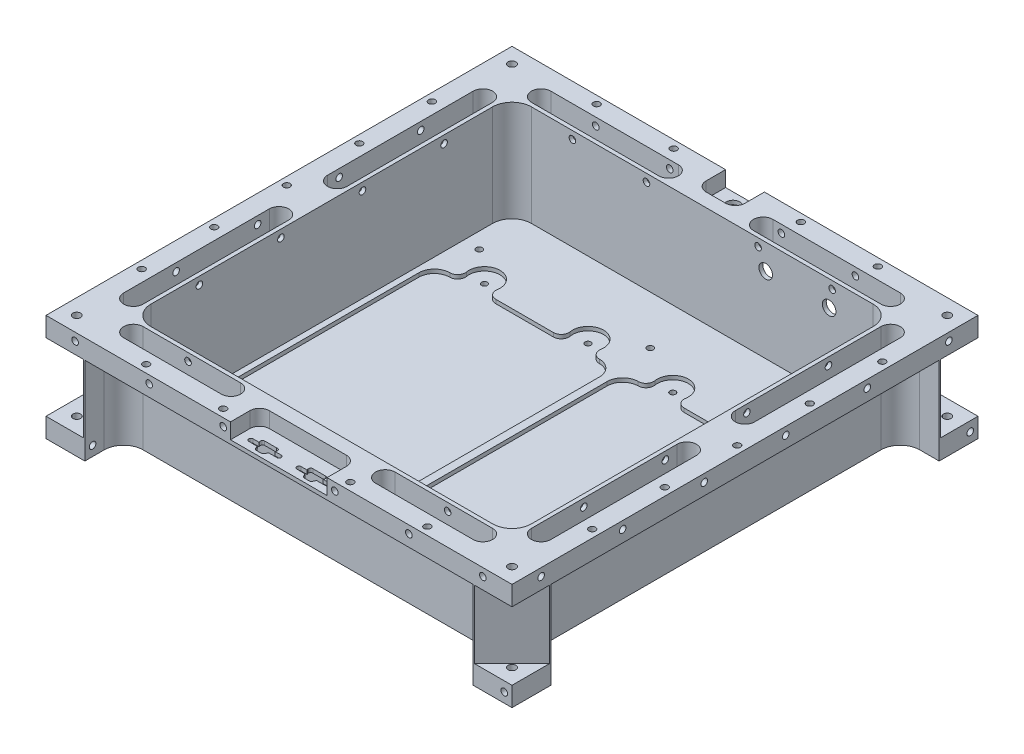
SolidWorks part; units mm, degrees
note: '?' marks a value the reader was unsure of. The reader was unsure of these and kept them because the rebuilt part matched: shared geometry of "Sketch29<3>".
ref_plane "Front" through (0, 0, 0) normal (0, 0, 1) x (1, 0, 0)
ref_plane "Top" through (0, 0, 0) normal (0, 1, 0) x (1, 0, 0)
ref_plane "Right" through (0, 0, 0) normal (1, 0, 0) x (0, 0, -1)
sketch "Sketch1" plane through (0, 0, 0) normal (0, 1, 0) x (1, 0, 0)
  line L1 (-120, 120) -> (120, 120)
  line L2 (-120, 120) -> (-120, -120)
  line L3 (-120, -120) -> (120, -120)
  line L4 (120, 120) -> (120, -120)
  dimension "D1" = 120
  dimension "D2" = 120
  dimension "D3" = 120
  dimension "D4" = 120
extrude "Boss-Extrude1" add sketch "Sketch1" along normal blind 55
sketch "Sketch2" plane through (0, 0, 0) normal (0, -1, 0) x (1, 0, 0)
  line L0 (-120, 120) -> (120, 120) construction
  line L1 (-120, 120) -> (-100, 120)
  line L2 (-120, 120) -> (-120, 100)
  line L3 (-120, 100) -> (-110, 100)
  line L4 (-100, 120) -> (-100, 110)
  line L5 (-120, -120) -> (-120, 120) construction
  line L6 (-100, 90) -> (-100, -90)
  line L7 (-90, 100) -> (90, 100)
  line L8 (0, -29.9157) -> (0, 29.9157) construction
  line L9 (0, 29.9157) -> (0, -29.9157) construction
  line L10 (30.6599, 0) -> (-30.6599, 0) construction
  line L11 (100, 90) -> (100, -90)
  line L12 (100, 120) -> (100, 110)
  line L13 (120, 100) -> (110, 100)
  line L14 (120, 120) -> (120, 100)
  line L15 (120, 120) -> (100, 120)
  line L16 (120, -120) -> (100, -120)
  line L17 (120, -120) -> (120, -100)
  line L18 (120, -100) -> (110, -100)
  line L19 (100, -120) -> (100, -110)
  line L20 (-90, -100) -> (90, -100)
  line L21 (-100, -120) -> (-100, -110)
  line L22 (-120, -100) -> (-110, -100)
  line L23 (-120, -120) -> (-120, -100)
  line L24 (-120, -120) -> (-100, -120)
  line L26 (-120, 120) -> (120, 120)
  line L27 (-120, 120) -> (-120, -120)
  line L28 (-120, -120) -> (120, -120)
  line L29 (120, 120) -> (120, -120)
  arc A0 (-100, 90) -> (-110, 100) centre (-110, 90) ccw
  arc A1 (-100, 110) -> (-90, 100) centre (-90, 110) ccw
  arc A2 (100, 110) -> (90, 100) centre (90, 110) cw
  arc A3 (100, 90) -> (110, 100) centre (110, 90) cw
  arc A4 (100, -90) -> (110, -100) centre (110, -90) ccw
  arc A5 (100, -110) -> (90, -100) centre (90, -110) ccw
  arc A6 (-100, -110) -> (-90, -100) centre (-90, -110) cw
  arc A7 (-100, -90) -> (-110, -100) centre (-110, -90) cw
  point P16 (-100, 0)
  point P26 (0, 100)
  point P32 (0, 0)
  point P47 (100, 0)
  point P50 (0, -100)
  line M1 (-120, 120) -> (-120, -120)
  line M2 (-120, -120) -> (120, -120)
  line M3 (120, -120) -> (120, 120)
  line M4 (120, 120) -> (-120, 120)
  dimension "D3" = 20
  dimension "D4" = 20
extrude "Cut-Extrude1" cut sketch "Sketch2" against normal blind 45 contours A7 L6 A0 L3 L22 M1 | A2 L12 L4 A1 L7 M4 | A6 L21 L19 A5 L20 M2 | L11 A4 L18 L13 A3 M3
ref_plane "Plane1" through (0, 10, 0) normal (0, 1, 0) x (1, 0, 0)
sketch "Sketch3" plane through (0, 10, 0) normal (0, 1, 0) x (1, 0, 0)
  line L0 (-120, 100.6173) -> (-100.6173, 120)
  line L1 (-120, 120) -> (-120, 100) construction
  line L2 (-100, 120) -> (-120, 120) construction
  line L3 (-112.0764, 112.0764) -> (0, 0) construction
  line L4 (-120, 100) -> (-110, 100) construction
  line L5 (-120, 100.6173) -> (-120, 120)
  line L6 (-120, 120) -> (-100.6173, 120)
  circle A0 centre (-112.0764, 112.0764) radius 2
  dimension "D1" = 4
  dimension "D2" = 158.5
  dimension "D3" = 2.5
  dimension "D4" = 45
extrude "Cut-Extrude2" cut sketch "Sketch3" along normal blind 35
ref_axis "Axis1" through (0, 0, 0) along (0, 1, 0)?
pattern_circular "CirPattern1" count 4 every 90 about axis through (0, 0, 0) along (0, 1, 0) of "Cut-Extrude2"
sketch "Sketch4" plane through (0, 55, 0) normal (0, 1, 0) x (1, 0, 0)
  line L0 (-90, 100) -> (90, 100) construction
  line L1 (-88, 98) -> (88, 98)
  line L2 (-98, 88) -> (-98, -88)
  line L3 (-88, -98) -> (88, -98)
  line L4 (98, 88) -> (98, -88)
  line L5 (-100, -90) -> (-100, 90) construction
  line L6 (-90, -100) -> (90, -100) construction
  line L7 (100, -90) -> (100, 90) construction
  line L9 (-90, 100) -> (-24.36, 100)
  line L10 (-90, 100) -> (-90, 110)
  line L11 (-90, 110) -> (-24.36, 110)
  line L12 (-24.36, 100) -> (-24.36, 110)
  line L13 (24.36, 100) -> (90, 100)
  line L14 (24.36, 100) -> (24.36, 110)
  line L15 (24.36, 110) -> (90, 110)
  line L16 (90, 100) -> (90, 110)
  line L17 (-100, 90) -> (-110, 90)
  line L18 (-100, 90) -> (-100, 15)
  line L19 (-100, 15) -> (-110, 15)
  line L20 (-110, 90) -> (-110, 15)
  line L21 (-100, -15) -> (-110, -15)
  line L22 (-100, -15) -> (-100, -90)
  line L23 (-100, -90) -> (-110, -90)
  line L24 (-110, -15) -> (-110, -90)
  line L25 (120, -120) -> (120, 120) construction
  line L26 (-120, 120) -> (-120, -120) construction
  line L27 (120, 120) -> (-120, 120) construction
  line L29 (-120, -120) -> (120, -120) construction
  line L30 (-120, -100) -> (-120, -120) construction
  line L31 (-90, -100) -> (-39.74, -100)
  line L32 (-90, -100) -> (-90, -110)
  line L33 (-90, -110) -> (-39.74, -110)
  line L34 (-39.74, -100) -> (-39.74, -110)
  line L35 (120, -100.6173) -> (120, -120) construction
  line L36 (39.74, -100) -> (90, -100)
  line L37 (39.74, -100) -> (39.74, -110)
  line L38 (39.74, -110) -> (90, -110)
  line L39 (90, -100) -> (90, -110)
  line L40 (0, 0) -> (0, 43.1053) construction
  line L41 (100, -90) -> (110, -90)
  line L42 (100, -15) -> (100, -90)
  line L43 (110, -15) -> (110, -90)
  line L44 (100, -15) -> (110, -15)
  line L45 (100, 15) -> (110, 15)
  line L46 (100, 90) -> (100, 15)
  line L47 (110, 90) -> (110, 15)
  arc A0 (-98, -88) -> (-88, -98) centre (-88, -88) ccw
  arc A1 (88, -98) -> (98, -88) centre (88, -88) ccw
  arc A2 (88, 98) -> (98, 88) centre (88, 88) cw
  arc A3 (-88, 98) -> (-98, 88) centre (-88, 88) ccw
  circle A4 centre (-90, 105) radius 5
  circle A5 centre (-24.36, 105) radius 5
  circle A6 centre (24.36, 105) radius 5
  circle A7 centre (90, 105) radius 5
  circle A8 centre (-105, 90) radius 5
  circle A9 centre (-105, 15) radius 5
  circle A10 centre (-105, -15) radius 5
  circle A11 centre (-105, -90) radius 5
  circle A12 centre (-90, -105) radius 5
  circle A13 centre (-39.74, -105) radius 5
  circle A14 centre (39.74, -105) radius 5
  circle A15 centre (90, -105) radius 5
  circle A16 centre (105, -90) radius 5
  circle A17 centre (105, -15) radius 5
  circle A18 centre (105, 15) radius 5
  circle A19 centre (105, 90) radius 5
  point P8 (0, -100)
  point P69 (-120, -110)
  point P80 (120, -110.3087)
  dimension "D5" = 10
  dimension "D1" = 2
  dimension "D2" = 2
  dimension "D3" = 2
  dimension "D4" = 2
  dimension "D6" = 10
  dimension "D7" = 10
  dimension "D8" = 10
  dimension "D9" = 10
  dimension "D10" = 75
  dimension "D11" = 75
  dimension "D12" = 65.64
  dimension "D13" = 65.64
  dimension "D14" = 30
  dimension "D15" = 30
  dimension "D16" = 30
  dimension "D17" = 30
  dimension "D18" = 50.26
  dimension "D19" = 30
  dimension "D20" = 50.26
  dimension "D21" = 10
  dimension "D22" = 30
  dimension "D23" = 10
extrude "Cut-Extrude3" cut sketch "Sketch4" against normal blind 52
sketch "Sketch5" plane through (0, 55, 0) normal (0, 1, 0) x (1, 0, 0)
  line L0 (-120, -120) -> (120, -120) construction
  line L1 (-24.74, -120) -> (24.74, -120)
  line L2 (-24.74, -120) -> (-24.74, -104.3329)
  line L3 (-24.74, -104.3329) -> (24.74, -104.3329)
  line L4 (24.74, -120) -> (24.74, -104.3329)
  line L5 (120, -120) -> (120, 120) construction
  line L6 (-120, 120) -> (-120, -120) construction
  line L7 (120, 120) -> (-120, 120) construction
  line L9 (0, 0) -> (-35.1249, 0) construction
  line L10 (0, 0) -> (0, 32.8924) construction
  point P7 (-116, 74.72)
  point P8 (-116, 37.36)
  point P9 (-116, 0)
  point P10 (-116, -37.36)
  point P11 (-116, -74.72)
  point P12 (116, -74.72)
  point P13 (116, -37.36)
  point P14 (116, 0)
  point P15 (116, 37.36)
  point P16 (116, 74.72)
  point P17 (-72.41, 116)
  point P18 (-32.74, 116)
  point P19 (32.74, 116)
  point P20 (72.41, 116)
  point P21 (72.41, -116)
  point P22 (32.74, -116)
  point P23 (-32.74, -116)
  point P24 (-72.41, -116)
  dimension "D1" = 49.48
  dimension "D2" = 24.74
  dimension "D3" = 47.59
  dimension "D4" = 39.67
  dimension "D5" = 4
  dimension "D6" = 47.59
  dimension "D7" = 39.67
  dimension "D8" = 45.28
  dimension "D9" = 37.36
  dimension "D10" = 45.28
  dimension "D11" = 37.36
  dimension "D12" = 0
  dimension "D13" = 4
hole_wizard "M3 Clearance Hole2" positions "Sketch8" profile "Sketch9" hole size "M3" standard "AS" end condition through all
sketch "Sketch8" plane through (0, 0, 0) normal (0, 1, 0) x (1, 0, 0)
  point P0 (-116, 74.72)
  point P3 (-116, 37.36)
  point P6 (-116, 0)
  point P9 (-116, -37.36)
  point P12 (-116, -74.72)
  point P15 (-72.41, -116)
  point P18 (-32.74, -116)
  point P21 (32.74, -116)
  point P24 (72.41, -116)
  point P27 (116, -74.72)
  point P30 (116, -37.36)
  point P33 (116, 0)
  point P36 (116, 37.36)
  point P39 (116, 74.72)
  point P42 (72.41, 116)
  point P45 (32.74, 116)
  point P48 (-32.74, 116)
  point P51 (-72.41, 116)
sketch "Sketch9" plane through (-116, 0, -74.72) normal (1, 0, 0) x (0, 0, -1)
  line L0 (0, 0) -> (0, 55)
  line L1 (0, 55) -> (1.7, 55)
  line L2 (1.7, 55) -> (1.7, 0)
  line L5 (1.7, 0) -> (0, 0)
  line L11 (0, -6.35) -> (0, 107.95) construction
  dimension "Thru Hole Dia." = 3.4
  dimension "Thru Hole Depth" = 55
sketch "Sketch10" plane through (0, 3, 0) normal (0, 1, 0) x (1, 0, 0)
  line L0 (-98, 88) -> (-98, -88) construction
  line L1 (-2, 0) -> (-95, 0) construction
  line L2 (-95, 47) -> (-95, -47)
  line L3 (-63.3357, -55) -> (-33.6643, -55)
  line L4 (-2, 47) -> (-2, -47)
  line L5 (-48.5, 0) -> (-48.5, 55) construction
  line L6 (-63.3357, 55) -> (-33.6643, 55)
  line L7 (-63.3357, -55) -> (-33.6643, -55)
  line L8 (0, 0) -> (0, 32.8924) construction
  line L9 (48.5, 0) -> (48.5, 55) construction
  line L10 (2, 0) -> (95, 0) construction
  line L11 (63.3357, -55) -> (33.6643, -55)
  line L12 (63.3357, 55) -> (33.6643, 55)
  line L13 (2, 47) -> (2, -47)
  line L14 (63.3357, -55) -> (33.6643, -55)
  line L15 (95, 47) -> (95, -47)
  arc A0 (-67.2797, 59.6667) -> (-83.0559, 59.6667) centre (-75.1678, 61) ccw
  arc A1 (-67.2797, 59.6667) -> (-63.3357, 55) centre (-63.3357, 59) ccw
  arc A2 (-87, 55) -> (-83.0559, 59.6667) centre (-87, 59) ccw
  arc A3 (-10, -55) -> (-2, -47) centre (-10, -47) ccw
  arc A4 (-95, -47) -> (-87, -55) centre (-87, -47) ccw
  arc A5 (-10, 55) -> (-2, 47) centre (-10, 47) cw
  arc A6 (-87, 55) -> (-95, 47) centre (-87, 47) ccw
  arc A7 (-10, 55) -> (-13.9441, 59.6667) centre (-10, 59) cw
  arc A8 (-29.7203, 59.6667) -> (-33.6643, 55) centre (-33.6643, 59) cw
  arc A9 (-29.7203, 59.6667) -> (-13.9441, 59.6667) centre (-21.8322, 61) cw
  arc A10 (-29.7203, -59.6667) -> (-13.9441, -59.6667) centre (-21.8322, -61) ccw
  arc A11 (-29.7203, -59.6667) -> (-33.6643, -55) centre (-33.6643, -59) ccw
  arc A12 (-10, -55) -> (-13.9441, -59.6667) centre (-10, -59) ccw
  arc A13 (-87, -55) -> (-83.0559, -59.6667) centre (-87, -59) cw
  arc A14 (-67.2797, -59.6667) -> (-63.3357, -55) centre (-63.3357, -59) cw
  arc A15 (-67.2797, -59.6667) -> (-83.0559, -59.6667) centre (-75.1678, -61) cw
  arc A16 (67.2797, -59.6667) -> (83.0559, -59.6667) centre (75.1678, -61) ccw
  arc A17 (67.2797, -59.6667) -> (63.3357, -55) centre (63.3357, -59) ccw
  arc A18 (87, -55) -> (83.0559, -59.6667) centre (87, -59) ccw
  arc A19 (10, -55) -> (13.9441, -59.6667) centre (10, -59) cw
  arc A20 (29.7203, -59.6667) -> (33.6643, -55) centre (33.6643, -59) cw
  arc A21 (29.7203, -59.6667) -> (13.9441, -59.6667) centre (21.8322, -61) cw
  arc A22 (29.7203, 59.6667) -> (13.9441, 59.6667) centre (21.8322, 61) ccw
  arc A23 (29.7203, 59.6667) -> (33.6643, 55) centre (33.6643, 59) ccw
  arc A24 (10, 55) -> (13.9441, 59.6667) centre (10, 59) ccw
  arc A25 (87, 55) -> (95, 47) centre (87, 47) cw
  arc A26 (10, 55) -> (2, 47) centre (10, 47) ccw
  arc A27 (95, -47) -> (87, -55) centre (87, -47) cw
  arc A28 (10, -55) -> (2, -47) centre (10, -47) cw
  arc A29 (87, 55) -> (83.0559, 59.6667) centre (87, 59) cw
  arc A30 (67.2797, 59.6667) -> (63.3357, 55) centre (63.3357, 59) cw
  arc A31 (67.2797, 59.6667) -> (83.0559, 59.6667) centre (75.1678, 61) cw
  point P18 (-2, 55)
  point P21 (-95, 55)
  point P88 (95, 55)
  point P89 (2, 55)
  dimension "D4" = 16
  dimension "D5" = 8
  dimension "D6" = 8
  dimension "D7" = 8
  dimension "D1" = 3
  dimension "D3" = 93
  dimension "D9" = 61
extrude "Cut-Extrude4" cut sketch "Sketch10" against normal blind 2 contours A15 A14 L3 A11 A10 A12 A3 L4 A5 A7 A9 A8 L6 A1 A0 A2 A6 L2 A4 A13 | A31 A30 L12 A23 A22 A24 A26 L13 A28 A19 A21 A20 L11 A17 A16 A18 A27 L15 A25 A29
sketch "Sketch13" plane through (0, 1, 0) normal (0, 1, 0) x (1, 0, 0)
  point P0 (-75.1678, 61)
  point P1 (-21.8322, 61)
  point P3 (21.8322, 61)
  point P5 (75.1678, 61)
  point P7 (75.1678, -61)
  point P9 (21.8322, -61)
  point P11 (-21.8322, -61)
  point P13 (-75.1678, -61)
  point P15 (-183.4443, -17.3111)
  point P17 (-190.7875, -19.9932)
  point P18 (-88, -73)
  point P19 (0, -73)
  point P20 (88, -73)
  dimension "D1" = 73
  dimension "D2" = 88
  dimension "D3" = 88
  dimension "D4" = 0
sketch "Sketch16" plane through (0, 0, 0) normal (0, -1, 0) x (1, 0, 0)
  line L0 (-88, 98) -> (88, 98)
  line L1 (-88, 98) -> (88, 98) construction
  line L2 (98, 88) -> (98, -88)
  line L3 (88, -98) -> (-88, -98)
  line L4 (-98, -88) -> (-98, 88)
  arc A0 (98, 88) -> (88, 98) centre (88, 88) ccw construction
  arc A1 (88, -98) -> (98, -88) centre (88, -88) ccw construction
  arc A2 (-98, -88) -> (-88, -98) centre (-88, -88) ccw construction
  arc A3 (-98, 88) -> (-88, 98) centre (-88, 88) cw
  arc A4 (-88, 98) -> (-98, 88) centre (-88, 88) ccw construction
  arc A5 (88, 98) -> (98, 88) centre (88, 88) cw
  arc A6 (88, -98) -> (98, -88) centre (88, -88) ccw
  arc A7 (-88, -98) -> (-98, -88) centre (-88, -88) cw
extrude "Extrude-Thin2" add sketch "Sketch16" along normal blind 2 thin
sketch "Sketch17" plane through (0, 0, 0) normal (0, -1, 0) x (1, 0, 0)
  line L3 (-88, 88) -> (88, 88)
  line L4 (-88, 88) -> (88, 88)
  line L12 (88, -88) -> (88, 88)
  line L13 (88, 88) -> (-88, 88)
  line L14 (-88, 88) -> (-88, -88)
  line L15 (-88, -88) -> (88, -88)
  line L16 (88, -88) -> (88, 88)
  line L17 (88, 88) -> (-88, 88)
  line L18 (-88, 88) -> (-88, -88)
  line L19 (-88, -88) -> (88, -88)
  line M2 (88, -88) -> (88, 88)
  line M3 (88, 88) -> (-88, 88)
  line M4 (-88, 88) -> (-88, -88)
  line M5 (-88, -88) -> (88, -88)
  dimension "D1" = 0
  dimension "D2" = 0
extrude "Boss-Extrude2" add sketch "Sketch17" along normal blind 2 contours M5 M2 M3 M4
hole_wizard "Ø3.0 (3) Diameter Hole1" positions "3DSketch2" profile "Sketch15" hole size "Ø3.0" standard "AS"
sketch3d "3DSketch2"
  point P0 (-75.1678, 1, -61)
  point P3 (-21.8322, 1, -61)
  point P6 (21.8322, 1, -61)
  point P9 (75.1678, 1, -61)
  point P12 (21.8322, 1, 61)
  point P15 (75.1678, 1, 61)
  point P18 (-21.8322, 1, 61)
  point P21 (-75.1678, 1, 61)
  point P24 (-88, 1, 73)
  point P27 (0, 1, 73)
  point P30 (88, 1, 73)
sketch "Sketch15" plane through (-75.1678, 1, -61) normal (1, 0, 0) x (0, 0, 1)
  line L0 (0, 0) -> (0, 3)
  line L1 (0, 3) -> (1.5, 3)
  line L2 (1.5, 3) -> (1.5, 0)
  line L5 (1.5, 0) -> (0, 0)
  line L11 (0, -6.35) -> (0, 107.95) construction
  dimension "Thru Hole Dia." = 3
  dimension "Thru Hole Depth" = 3
sketch "Sketch19" plane through (0, -2, 0) normal (0, -1, 0) x (1, 0, 0)
  line L0 (-5.099, 58) -> (5.099, 58)
  line L1 (38.5654, 58) -> (58.4346, 58)
  line L3 (0, 0) -> (-50.965, 0) construction
  line L8 (-58.4346, 58) -> (-38.5654, 58)
  line L9 (-63.3357, 55) -> (-33.6643, 55) construction
  line L12 (95, -88) -> (95, 88)
  line L13 (88, 95) -> (-88, 95)
  line L14 (-95, 88) -> (-95, -88)
  line L15 (-88, -95) -> (88, -95)
  line L16 (95, -88) -> (95, 88)
  line L17 (88, 95) -> (-88, 95)
  line L18 (-95, 88) -> (-95, -88)
  line L19 (-88, -95) -> (88, -95)
  arc A0 (-95, 70.8829) -> (-84.1181, 67.3948) centre (-89, 70.8829) ccw
  arc A1 (-38.5654, 58) -> (-32.6595, 62.9412) centre (-38.5654, 64) ccw
  arc A2 (32.6595, 62.9412) -> (11.0048, 62.9412) centre (21.8322, 61) ccw
  arc A4 (29.7203, 59.6667) -> (13.9441, 59.6667) centre (21.8322, 61) ccw construction
  arc A5 (84.1181, 67.3948) -> (64.3405, 62.9412) centre (75.1678, 61) ccw
  arc A6 (83.0559, 59.6667) -> (67.2797, 59.6667) centre (75.1678, 61) ccw construction
  arc A7 (84.1181, 67.3948) -> (95, 70.8829) centre (89, 70.8829) ccw
  arc A8 (-64.3405, 62.9412) -> (-84.1181, 67.3948) centre (-75.1678, 61) ccw
  arc A9 (-67.2797, 59.6667) -> (-83.0559, 59.6667) centre (-75.1678, 61) ccw construction
  arc A10 (-11.0048, 62.9412) -> (-32.6595, 62.9412) centre (-21.8322, 61) ccw
  arc A11 (-13.9441, 59.6667) -> (-29.7203, 59.6667) centre (-21.8322, 61) ccw construction
  arc A12 (95, 88) -> (88, 95) centre (88, 88) ccw
  arc A13 (-88, 95) -> (-95, 88) centre (-88, 88) ccw
  arc A14 (-95, -88) -> (-88, -95) centre (-88, -88) ccw
  arc A15 (88, -95) -> (95, -88) centre (88, -88) ccw
  arc A16 (95, 88) -> (88, 95) centre (88, 88) ccw
  arc A17 (-88, 95) -> (-95, 88) centre (-88, 88) ccw
  arc A18 (-95, -88) -> (-88, -95) centre (-88, -88) ccw
  arc A19 (88, -95) -> (95, -88) centre (88, -88) ccw
  arc A20 (-64.3405, 62.9412) -> (-58.4346, 58) centre (-58.4346, 64) ccw
  arc A21 (-11.0048, 62.9412) -> (-5.099, 58) centre (-5.099, 64) ccw
  arc A22 (5.099, 58) -> (11.0048, 62.9412) centre (5.099, 64) ccw
  arc A23 (32.6595, 62.9412) -> (38.5654, 58) centre (38.5654, 64) ccw
  arc A24 (58.4346, 58) -> (64.3405, 62.9412) centre (58.4346, 64) ccw
  circle M17 centre (-88, 73) radius 1.5
  circle M18 centre (0, 73) radius 1.5
  circle M19 centre (88, 73) radius 1.5
  dimension "D2" = 3
  dimension "D3" = 3
  dimension "D5" = 12
  dimension "D6" = 12
  dimension "D7" = 12
  dimension "D8" = 3
  dimension "D9" = 3
  dimension "D10" = 12
  dimension "D11" = 12
  dimension "D12" = 12
  dimension "D4" = 3
  dimension "D1" = 3
extrude "Cut-Extrude5" cut sketch "Sketch19" against normal blind 2 contours L1 A24 A5 A7 L16 A16 L17 A17 L18 A0 A8 A20 L8 A1 A10 A21 L0 A22 A2 A23 M18 M19 M17
mirror "Mirror1" about plane through (0, 0, 0) normal (0, 0, 1) of "Cut-Extrude5"
sketch "Sketch20" plane through (0, -2, 0) normal (0, -1, 0) x (1, 0, 0)
  circle A0 centre (-88, -73) radius 1.5
  circle A1 centre (0, -73) radius 1.5
  circle A2 centre (88, -73) radius 1.5
extrude "Cut-Extrude6" cut sketch "Sketch20" against normal blind 2
sketch "Sketch21" plane through (0, 55, 0) normal (0, 1, 0) x (1, 0, 0)
  line L0 (0, 0) -> (131.4952, -131.4952) construction
  circle A0 centre (112.0764, -112.0764) radius 2
  dimension "D2" = 4
  dimension "D1" = 158.5
extrude "Cut-Extrude7" cut sketch "Sketch21" against normal through all
pattern_circular "CirPattern2" count 4 every 90 about axis through (0, 0, 0) along (0, 1, 0) of "Cut-Extrude7"
sketch "Sketch22" plane through (120, 0, 0) normal (1, 0, 0) x (0, 0, -1)
  line L0 (-120, 55) -> (120, 55) construction
  line L1 (100, 0) -> (120, 0) construction
  line L2 (120, 10) -> (120, 0) construction
  point P0 (-105, 51)
  point P1 (-63, 51)
  point P2 (-21, 51)
  point P3 (21, 51)
  point P4 (63, 51)
  point P5 (105, 51)
  point P9 (116, 5)
  dimension "D1" = 21
  dimension "D2" = 21
  dimension "D3" = 63
  dimension "D4" = 105
  dimension "D5" = 63
  dimension "D6" = 105
  dimension "D7" = 4
  dimension "D8" = 5
  dimension "D9" = 4
sketch "Sketch23" plane through (-120, 0, 0) normal (-1, 0, 0) x (0, 0, 1)
  line L0 (100, 0) -> (120, 0) construction
  line L1 (120, 10) -> (120, 0) construction
  point P0 (-105, 51)
  point P1 (-63, 51)
  point P3 (-21, 51)
  point P5 (21, 51)
  point P7 (63, 51)
  point P9 (105, 51)
  point P11 (116, 5)
  point P15 (120, 5)
  dimension "D1" = 5
  dimension "D2" = 4
hole_wizard "M3 Clearance Hole3" positions "3DSketch3" profile "Sketch25" hole size "M3" standard "AS"
sketch3d "3DSketch3"
  point P0 (120, 51, 105)
  point P3 (120, 51, 63)
  point P6 (120, 51, 21)
  point P9 (120, 51, -21)
  point P12 (120, 51, -63)
  point P15 (120, 51, -105)
  point P19 (-120, 51, 105)
  point P22 (-120, 51, 63)
  point P25 (-120, 51, 21)
  point P28 (-120, 51, -21)
  point P31 (-120, 51, -63)
  point P34 (-120, 51, -105)
  point P38 (-120, 5, 116)
  point P41 (120, 5, -116)
sketch "Sketch25" plane through (120, 51, 105) normal (0, 1, 0) x (0, 0, -1)
  line L0 (0, 0) -> (0, 23.0215)
  line L1 (0, 23.0215) -> (1.7, 22)
  line L2 (1.7, 22) -> (1.7, 0)
  line L5 (1.7, 0) -> (0, 0)
  line L10 (0, 23.0215) -> (-1.7, 22) construction
  line L11 (0, -6.35) -> (0, 107.95) construction
  dimension "Hole Dia." = 3.4
  dimension "Hole Depth" = 22
  dimension "Drill Angle" = 118
sketch "Sketch26" plane through (0, 0, 120) normal (0, 0, 1) x (1, 0, 0)
  line L0 (-120, 55) -> (120, 55) construction
  line L1 (0, 0) -> (0, 67.5321) construction
  line L2 (120, 10) -> (120, 0) construction
  line L3 (100, 0) -> (120, 0) construction
  point P0 (-105, 51)
  point P1 (-66.87, 51)
  point P2 (-28.74, 51)
  point P4 (28.74, 51)
  point P5 (66.87, 51)
  point P6 (105, 51)
  point P7 (116, 5)
  dimension "D1" = 4
  dimension "D2" = 28.74
  dimension "D3" = 38.13
  dimension "D4" = 38.13
  dimension "D5" = 28.74
  dimension "D6" = 38.13
  dimension "D7" = 38.13
  dimension "D8" = 4
  dimension "D9" = 5
sketch "Sketch27" plane through (0, 0, -120) normal (0, 0, -1) x (-1, 0, 0)
  line L0 (120, 10) -> (120, 0) construction
  line L1 (100, 0) -> (120, 0) construction
  point P0 (-105, 51)
  point P1 (-66.87, 51)
  point P3 (-28.74, 51)
  point P5 (28.74, 51)
  point P7 (66.87, 51)
  point P9 (105, 51)
  point P11 (116, 5)
  dimension "D1" = 4
  dimension "D2" = 5
hole_wizard "M3 Clearance Hole4" positions "3DSketch4" profile "Sketch28" hole size "M3" standard "AS"
sketch3d "3DSketch4"
  point P0 (105, 51, -120)
  point P3 (66.87, 51, -120)
  point P6 (28.74, 51, -120)
  point P9 (-28.74, 51, -120)
  point P12 (-66.87, 51, -120)
  point P15 (-105, 51, -120)
  point P18 (-116, 5, -120)
  point P21 (-105, 51, 120)
  point P24 (-66.87, 51, 120)
  point P27 (-28.74, 51, 120)
  point P30 (28.74, 51, 120)
  point P33 (66.87, 51, 120)
  point P36 (105, 51, 120)
  point P39 (116, 5, 120)
sketch "Sketch28" plane through (105, 51, -120) normal (1, 0, 0) x (0, 1, 0)
  line L0 (0, 0) -> (0, 23.0215)
  line L1 (0, 23.0215) -> (1.7, 22)
  line L2 (1.7, 22) -> (1.7, 0)
  line L5 (1.7, 0) -> (0, 0)
  line L10 (0, 23.0215) -> (-1.7, 22) construction
  line L11 (0, -6.35) -> (0, 107.95) construction
  dimension "Hole Dia." = 3.4
  dimension "Hole Depth" = 22
  dimension "Drill Angle" = 118
sketch "Sketch29" plane through (0, 45, 0) normal (0, 1, 0) x (1, 0, 0)
  line L0 (120, 120) -> (-120, 120) construction
  line L1 (-10, 120) -> (10, 120)
  line L2 (-10, 120) -> (-10, 113.75)
  line L3 (-10, 113.75) -> (-10, 110)
  line L4 (10, 120) -> (10, 113.75)
  line L5 (-10, 120) -> (-10, 110)
  line L6 (10, 120) -> (10, 110)
  line L7 (-5, 105) -> (5, 105)
  circle A0 centre (0, 113.75) radius 3.5
  arc A1 (-10, 110) -> (-5, 105) centre (-5, 110) ccw
  arc A4 (5, 105) -> (10, 110) centre (5, 110) ccw
  line M25 (-100, 120) -> (100, 120)
  dimension "D4" = 7
  dimension "D6" = 10
  dimension "D1" = 6.25
  dimension "D2" = 20
  dimension "D3" = 10
  dimension "D5" = 10
extrude "Cut-Extrude8" cut sketch "Sketch29" along normal blind 8 from offset 2 contours A4 L7 A1 L3 L2 L4 L6 A0 M25
extrude "Cut-Extrude9" cut sketch "Sketch29<3>" along normal blind 10 contours A0
sketch "Sketch29<3>" plane through (0, 45, 0) normal (0, 1, 0) x (1, 0, 0) same geometry as "Sketch29"
sketch "Sketch30" plane through (0, 45, 0) normal (0, 1, 0) x (1, 0, 0)
  line L0 (-120, -120) -> (120, -120) construction
  line L1 (-24.99, -110) -> (24.74, -110)
  line L2 (-24.99, -110) -> (-24.99, -120)
  line L3 (-24.99, -120) -> (24.74, -120)
  line L4 (24.74, -110) -> (24.74, -120)
  line L5 (-19.99, -105) -> (19.74, -105)
  circle A0 centre (-19.99, -110) radius 5
  circle A1 centre (19.74, -110) radius 5
  line M23 (100, -120) -> (-100, -120)
  dimension "D4" = 10
  dimension "D5" = 10
  dimension "D1" = 24.74
  dimension "D2" = 24.99
  dimension "D3" = 10
extrude "Cut-Extrude10" cut sketch "Sketch30" along normal blind 8 from offset 2 contours L1 A1 L4 L2 A0 M23 | L5 A1 L1 A0
sketch "DE Subminiature" plane through (0, 0, 100) normal (0, 0, 1) x (1, 0, 0)
  line L0 (0, 0) -> (0, 30.87) construction
  line L1 (0.3133, 30.87) -> (-49999.6867, 30.87) construction
  point P3 (-45, 30.87)
  point P6 (45, 30.87)
  dimension "D1" = 45
  dimension "D2" = 45
sketch "Sketch33" plane through (0, 0, -98) normal (0, 0, 1) x (1, 0, 0)
  line L0 (-88, 55) -> (88, 55) construction
  point P0 (65.34, 42)
  point P1 (32.67, 42)
  dimension "D1" = 32.67
  dimension "D2" = 32.67
  dimension "D3" = 13
hole_wizard "Ø7.0 (7) Diameter Hole1" positions "3DSketch5" profile "Sketch34" hole size "Ø7.0" standard "AS"
sketch3d "3DSketch5"
  point P0 (32.67, 42, -98)
  point P3 (65.34, 42, -98)
sketch "Sketch34" plane through (32.67, 42, -98) normal (1, 0, 0) x (0, -1, 0)
  line L0 (0, 0) -> (0, 2)
  line L1 (0, 2) -> (3.5, 2)
  line L2 (3.5, 2) -> (3.5, 0)
  line L5 (3.5, 0) -> (0, 0)
  line L11 (0, -6.35) -> (0, 107.95) construction
  dimension "Thru Hole Dia." = 7
  dimension "Thru Hole Depth" = 2
sketch "DE microminiature" plane through (0, 47, 0) normal (0, 1, 0) x (1, 0, 0)
  line L0 (-15.6566, -111.7174) -> (-9.4896, -111.7174)
  line L1 (-13.6374, -118.07) -> (-11.1026, -118.07)
  line L2 (-16.6723, -113.2954) -> (-14.653, -117.4354) construction
  line L3 (-19.61, -113.74) -> (-5.13, -113.74) construction
  line L4 (-8.0603, -113.2801) -> (-10.087, -117.4354) construction
  line L5 (-19.61, -116) -> (-5.13, -116) construction
  line L6 (-16.6723, -113.2954) -> (-16.4554, -113.74)
  line L7 (-16.4554, -113.74) -> (-19.61, -113.74)
  line L8 (-8.0603, -113.2801) -> (-8.2846, -113.74)
  line L9 (-8.2846, -113.74) -> (-5.13, -113.74)
  line L10 (-5.13, -116) -> (-9.3869, -116)
  line L11 (-9.3869, -116) -> (-10.087, -117.4354)
  line L12 (-14.653, -117.4354) -> (-15.3531, -116)
  line L13 (-15.3531, -116) -> (-19.61, -116)
  line L14 (9.0834, -111.67) -> (15.6566, -111.67)
  line L15 (11.1026, -118.07) -> (13.6374, -118.07)
  line L16 (8.0677, -113.2954) -> (10.087, -117.4354) construction
  line L17 (5.13, -113.74) -> (19.61, -113.74) construction
  line L18 (16.6723, -113.2954) -> (14.653, -117.4354) construction
  line L19 (5.13, -116) -> (19.61, -116) construction
  line L20 (8.0677, -113.2954) -> (8.2846, -113.74)
  line L21 (8.2846, -113.74) -> (5.13, -113.74)
  line L22 (16.6723, -113.2954) -> (16.4554, -113.74)
  line L23 (16.4554, -113.74) -> (19.61, -113.74)
  line L24 (19.61, -116) -> (15.3531, -116)
  line L25 (15.3531, -116) -> (14.653, -117.4354)
  line L26 (10.087, -117.4354) -> (9.3869, -116)
  line L27 (9.3869, -116) -> (5.13, -116)
  line L28 (24.74, -120) -> (-24.99, -120) construction
  line L30 (-116, 0) -> (116, 0) construction
  line L31 (116, 0) -> (0, 0) construction
  line L32 (0, 0) -> (0, -144.3432) construction
  arc A0 (-19.61, -113.74) -> (-19.61, -116) centre (-19.61, -114.87) ccw
  arc A1 (-5.13, -113.74) -> (-5.13, -116) centre (-5.13, -114.87) cw
  arc A2 (-9.4896, -111.7174) -> (-8.0603, -113.2801) centre (-9.0836, -112.781) cw
  arc A3 (-15.6566, -111.7174) -> (-16.6723, -113.2954) centre (-15.6566, -112.8332) ccw
  arc A4 (-10.087, -117.4354) -> (-11.1026, -118.07) centre (-11.1026, -116.94) cw
  arc A5 (-14.653, -117.4354) -> (-13.6374, -118.07) centre (-13.6374, -116.94) ccw
  arc A6 (5.13, -113.74) -> (5.13, -116) centre (5.13, -114.87) ccw
  arc A7 (19.61, -113.74) -> (19.61, -116) centre (19.61, -114.87) cw
  arc A8 (15.6566, -111.67) -> (16.6723, -113.2954) centre (15.6566, -112.8) cw
  arc A9 (9.0834, -111.67) -> (8.0677, -113.2954) centre (9.0834, -112.8) ccw
  arc A10 (14.653, -117.4354) -> (13.6374, -118.07) centre (13.6374, -116.94) cw
  arc A11 (10.087, -117.4354) -> (11.1026, -118.07) centre (11.1026, -116.94) ccw
  point P2 (12.37, -114.87)
  point P4 (-12.37, -114.87)
  point P13 (-15.6566, -112.8332)
  point P14 (-9.0836, -112.781)
  point P21 (-13.6374, -116.94)
  point P22 (-11.1026, -116.94)
  point P37 (9.0834, -112.8)
  point P38 (15.6566, -112.8)
  point P45 (11.1026, -116.94)
  point P46 (13.6374, -116.94)
  dimension "D2" = 1.13
  dimension "D3" = 3.2
  dimension "D4" = 2.26
  dimension "D5" = 6.4
  dimension "D6" = 7.24
  dimension "D7" = 14.48
  dimension "D8" = 14.48
  dimension "D9" = 7.24
  dimension "D10" = 7.24
  dimension "D11" = 14.48
  dimension "D12" = 4
  dimension "D13" = 4
  dimension "D14" = 3.2866
  dimension "D15" = 12.37
  dimension "D16" = 6.5732
  dimension "D17" = 1.2674
  dimension "D18" = 2.5348
  dimension "D19" = 12.37
  dimension "D20" = 4.2569
  dimension "D21" = 4.2569
  dimension "D22" = 3.2866
  dimension "D23" = 6.5732
  dimension "D24" = 4.2569
  dimension "D25" = 4.2569
  dimension "D26" = 1.2674
  dimension "D27" = 2.5348
extrude "Cut-Extrude11" cut sketch "DE microminiature" against normal up to next
sketch "PCB Moutings" plane through (0, 3, 0) normal (0, 1, 0) x (1, 0, 0)
  line L0 (-166.6944, 73) -> (187.3553, 73) construction
  circle A0 centre (-89.831, 73) radius 1.6
  circle A1 centre (-1.831, 73) radius 1.6
  circle A2 centre (86.169, 73) radius 1.6
  dimension "D2" = 88
  dimension "D1" = 73
  dimension "D3" = 88
extrude "Cut-Extrude12" cut sketch "PCB Moutings" against normal up to next
sketch "DE Connector" plane through (0, 0, 100) normal (0, 0, 1) x (1, 0, 0)
  line L0 (-51.2426, 36.57) -> (-38.7574, 36.57)
  line L1 (-35.4583, 32.6383) -> (-36.287, 27.9383)
  line L2 (-39.5861, 25.17) -> (-50.4139, 25.17)
  line L3 (-53.713, 27.9383) -> (-54.5417, 32.6383)
  line L4 (200000.3133, 30.87) -> (-249999.6867, 30.87) construction
  line L5 (38.7704, 36.57) -> (51.2572, 36.57)
  line L6 (54.5584, 32.6502) -> (53.7471, 27.9502)
  line L7 (50.4459, 25.17) -> (39.6148, 25.17)
  line L9 (35.4732, 32.6277) -> (36.3176, 27.9277)
  arc A0 (-51.2426, 36.57) -> (-54.5417, 32.6383) centre (-51.2426, 33.22) ccw
  arc A1 (-35.4583, 32.6383) -> (-38.7574, 36.57) centre (-38.7574, 33.22) ccw
  arc A2 (-39.5861, 25.17) -> (-36.287, 27.9383) centre (-39.5861, 28.52) ccw
  arc A3 (-50.4139, 25.17) -> (-53.713, 27.9383) centre (-50.4139, 28.52) cw
  circle A4 centre (-57.495, 30.87) radius 1.52
  circle A5 centre (-32.5, 30.87) radius 1.52
  arc A6 (36.3176, 27.9277) -> (39.6148, 25.17) centre (39.6148, 28.52) ccw
  arc A7 (53.7471, 27.9502) -> (50.4459, 25.17) centre (50.4459, 28.52) cw
  arc A8 (54.5584, 32.6502) -> (51.2572, 36.57) centre (51.2572, 33.22) ccw
  arc A9 (38.7704, 36.57) -> (35.4732, 32.6277) centre (38.7704, 33.22) ccw
  circle A10 centre (32.5, 30.87) radius 1.52
  circle A11 centre (57.5, 30.87) radius 1.52
  dimension "D1" = 11.4
  dimension "D6" = 100
  dimension "D2" = 3.35
  dimension "D7" = 3.35
  dimension "D3" = 3.35
  dimension "D4" = 3.35
  dimension "D8" = 3.04
  dimension "D9" = 3.04
  dimension "D15" = 3.35
  dimension "D16" = 3.35
  dimension "D12" = 3.35
  dimension "D13" = 3.35
  dimension "D17" = 3.04
  dimension "D18" = 3.04
  dimension "D5" = 100
  dimension "D10" = 12.495
  dimension "D11" = 12.5
  dimension "D14" = 11.4
  dimension "D19" = 12.5
  dimension "D20" = 12.5
extrude "Cut-Extrude13" cut sketch "DE Connector" against normal up to next
